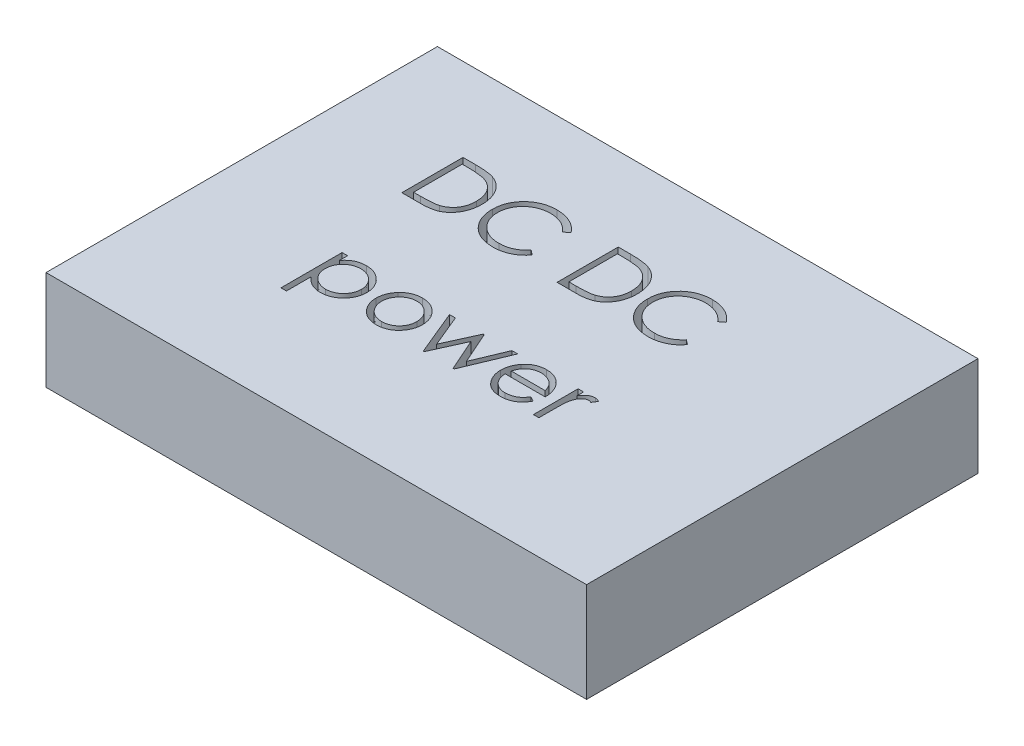
SolidWorks part; units mm, degrees
ref_plane "Front Plane" through (0, 0, 0) normal (0, 0, 1) x (1, 0, 0)
ref_plane "Top Plane" through (0, 0, 0) normal (0, 1, 0) x (1, 0, 0)
ref_plane "Right Plane" through (0, 0, 0) normal (1, 0, 0) x (0, 0, -1)
sketch "Sketch1" plane through (0, 0, 0) normal (0, 1, 0) x (1, 0, 0)
  line L1 (11.049, -8.001) -> (-11.049, -8.001)
  line L2 (11.049, -8.001) -> (11.049, 8.001)
  line L3 (11.049, 8.001) -> (-11.049, 8.001)
  line L4 (-11.049, -8.001) -> (-11.049, 8.001)
  line L5 (11.049, -8.001) -> (-11.049, 8.001) construction
  line L6 (11.049, 8.001) -> (-11.049, -8.001) construction
  point P0 (0, 0)
  dimension "D1" = 16.002
  dimension "D2" = 22.098
extrude "Boss-Extrude1" add sketch "Sketch1" along normal blind 4.064
sketch "Sketch2" plane through (0, 4.064, 0) normal (0, 1, 0) x (1, 0, 0)
  text T0 "DC DC\r\n power" font "Century Gothic" height 2.5
extrude "Cut-Extrude1" cut sketch "Sketch2" against normal blind 1
